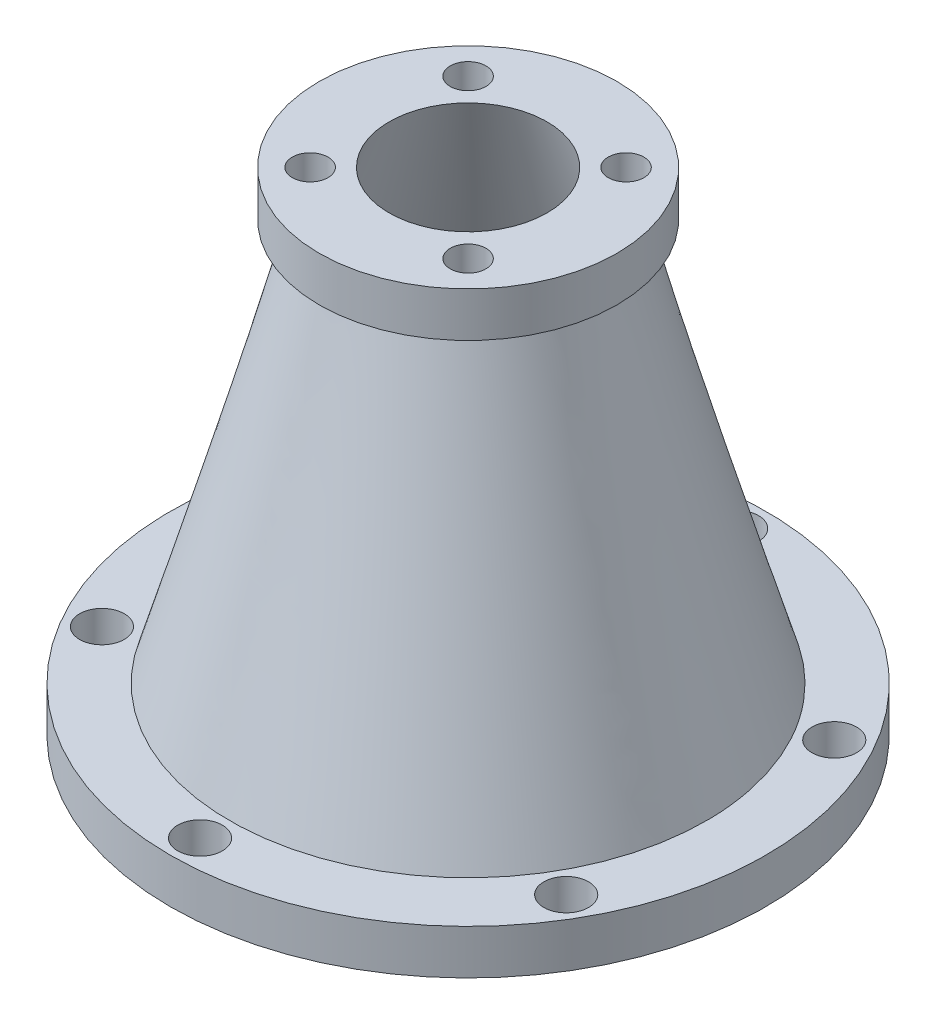
SolidWorks part; units mm, degrees
ref_plane "Front Plane" through (0, 0, 0) normal (0, 0, 1) x (1, 0, 0)
ref_plane "Top Plane" through (0, 0, 0) normal (0, 1, 0) x (1, 0, 0)
ref_plane "Right Plane" through (0, 0, 0) normal (1, 0, 0) x (0, 0, -1)
sketch "Sketch2" plane through (0, 0, 0) normal (0, 1, 0) x (1, 0, 0)
  circle A0 centre (0, 0) radius 200
ref_plane "Plane2" through (0, 300, 0) normal (0, 1, 0) x (1, 0, 0)
sketch "Sketch4" plane through (0, 300, 0) normal (0, 1, 0) x (1, 0, 0)
  circle A0 centre (0, 0) radius 100
extrude "Bottom  Flange" add sketch "Sketch2" along normal blind 30
extrude "Top Flange" add sketch "Sketch4" along normal blind 30 separate body contours A0
sketch "Sketch5" plane through (0, 300, 0) normal (0, 1, 0) x (1, 0, 0)
  circle A0 centre (0, 0) radius 85
sketch "Sketch6" plane through (0, 30, 0) normal (0, 1, 0) x (1, 0, 0)
  circle A0 centre (0, 0) radius 160
loft "Transition Body" add profiles "Sketch6", "Sketch5" connector at (-150.0932, 30, 55.4259) connector at (-84.9758, 300, 2.0293)
sketch "Bottom Flange Bolt Cut" plane through (0, 30, 0) normal (0, 1, 0) x (1, 0, 0)
  line L0 (0, 160) -> (0, 200) construction
  circle A0 centre (0, 0) radius 160 construction
  circle A1 centre (0, 0) radius 200 construction
  circle A2 centre (0, 180) radius 15
  circle A3 centre (155.8846, 90) radius 15
  circle A4 centre (155.8846, -90) radius 15
  circle A5 centre (0, -180) radius 15
  circle A6 centre (-155.8846, -90) radius 15
  circle A7 centre (-155.8846, 90) radius 15
  point P22 (0, 0)
  dimension "D1" = 6
sketch "Sketch9" plane through (0, 330, 0) normal (0, 1, 0) x (1, 0, 0)
  line L0 (0, -100) -> (0, 100) construction
  circle A0 centre (0, 0) radius 100 construction
sketch "Top Flange Bolt Cut" plane through (0, 330, 0) normal (0, 1, 0) x (1, 0, 0)
  line L0 (0, 0) -> (100, 0) construction
  line L1 (100, 0) -> (-100, 0) construction
  line L2 (0, 0) -> (0, -100) construction
  line L3 (0, 0) -> (0, 100) construction
  line L4 (0, 0) -> (70.7107, 70.7107) construction
  line L5 (35.3553, 35.3553) -> (70.7107, 70.7107) construction
  line L6 (53.033, 53.033) -> (70.7107, 70.7107) construction
  circle A0 centre (0, 0) radius 100 construction
  circle A1 centre (53.033, 53.033) radius 12
  circle A2 centre (53.033, -53.033) radius 12
  circle A3 centre (-53.033, -53.033) radius 12
  circle A4 centre (-53.033, 53.033) radius 12
  point P24 (0, 0)
  dimension "D1" = 4
sketch "Top Flange Cut" plane through (0, 330, 0) normal (0, 1, 0) x (1, 0, 0)
  circle A0 centre (0, 0) radius 50.6
sketch "Bottom Flange Cut" plane through (0, 0, 0) normal (0, 1, 0) x (1, 0, 0)
  circle A0 centre (0, 0) radius 160 construction
  circle A1 centre (0, 0) radius 160
sketch "Sketch16" plane through (0, 0, 0) normal (0, 0, 1) x (1, 0, 0)
  line L0 (0, 0) -> (0, 330) construction
  line L1 (0, 0) -> (0, 330)
  line L3 (0, 330) -> (-53.033, 330)
  line L5 (-41.033, 330) -> (-65.033, 330) construction
  line L6 (0, 0) -> (0, 330) construction
  line L7 (-53.033, 330) -> (-160, 0)
  line L8 (160, 0) -> (-160, 0) construction
  line L9 (-160, 0) -> (0, 0)
ref_axis "Axis2" through (0, -20, 0) along (0, 1, 0)
revolve "Cut-Revolve2" cut sketch "Sketch16" angle 360 about L1
extrude "Cut-Extrude3" cut sketch "Top Flange Bolt Cut" against normal blind 25
extrude "Cut-Extrude6" cut sketch "Bottom Flange Bolt Cut" against normal blind 96
